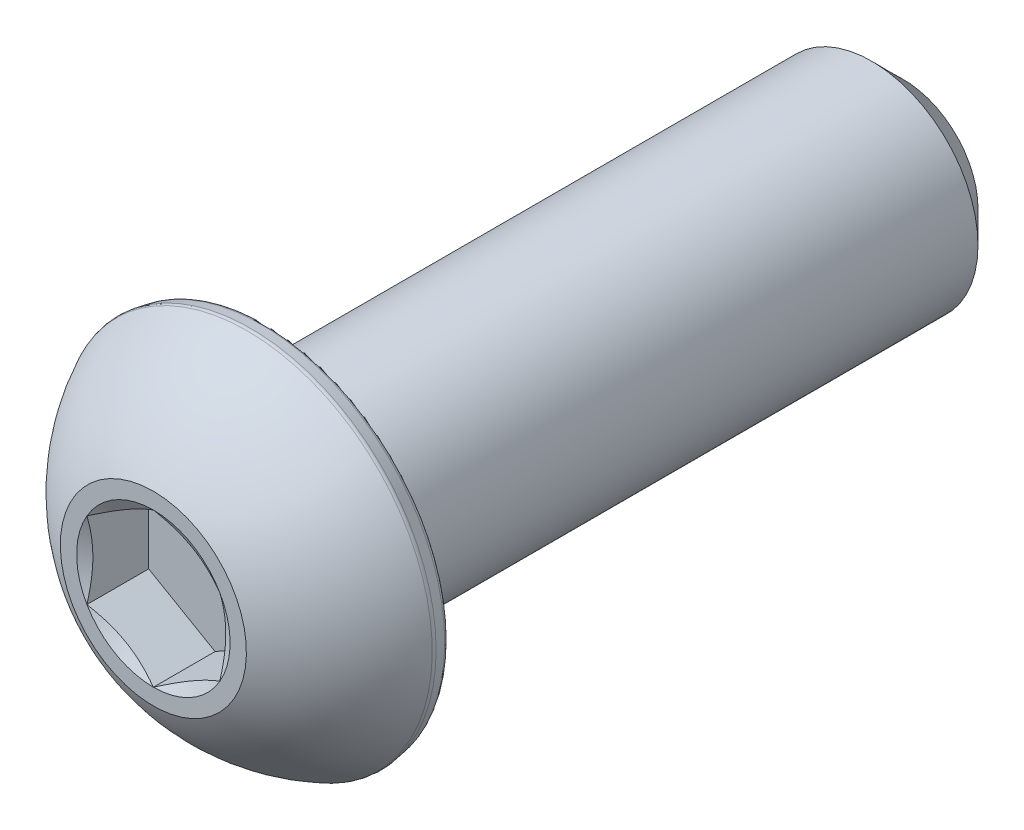
SolidWorks part; units mm, degrees
ref_plane "Front Plane" through (0, 0, 0) normal (0, 0, 1) x (1, 0, 0)
ref_plane "Top Plane" through (0, 0, 0) normal (0, 1, 0) x (1, 0, 0)
ref_plane "Right Plane" through (0, 0, 0) normal (1, 0, 0) x (0, 0, -1)
sketch "Sketch1" plane through (0, 0, 0) normal (1, 0, 0) x (0, 0, -1)
  line L0 (-11.2014, 0) -> (11.2014, 0) construction
  line L1 (-11.2014, 0) -> (-11.2014, 5.5499)
  line L2 (-11.2014, 5.5499) -> (-7.8486, 5.5499)
  line L3 (-7.8486, 5.5499) -> (-7.8486, 3.175)
  line L4 (-7.8486, 3.175) -> (11.2014, 3.175)
  line L5 (11.2014, 3.175) -> (11.2014, 0)
  point P2 (0, 0)
  point P4 (9.9314, 0)
  point P9 (9.2964, 3.175)
  point P10 (9.2964, -3.175)
  point P11 (11.2014, -3.175)
  point P15 (-9.3574, 0)
  dimension "Head Height" = 3.3528
  dimension "Head Diameter" = 11.0998
  dimension "Length" = 19.05
  dimension "Screw Size Decimal Equivalent" = 6.35
  dimension "Thread Pitch" = 1.27
  dimension "D1" = 1.905
  dimension "D2" = 1.844
sketch "Sketch2" plane through (0, 0, 0) normal (0, 0, 1) x (1, 0, 0)
  line L0 (0, 3.175) -> (0, 0) construction
  line L1 (0, 2.2914) -> (-1.9844, 1.1457)
  line L2 (-1.9844, 1.1457) -> (-1.9844, -1.1457)
  line L3 (-1.9844, -1.1457) -> (0, -2.2914)
  line L4 (0, -2.2914) -> (1.9844, -1.1457)
  line L5 (1.9844, -1.1457) -> (1.9844, 1.1457)
  line L6 (1.9844, 1.1457) -> (0, 2.2914)
  circle A0 centre (0, 0) radius 1.9844 construction
  circle A1 centre (0, 0) radius 2.7781
  point P10 (0, 2.7781)
  dimension "D1" = 5.5563
  dimension "Drive Size" = 3.9688
sketch "Sketch3" plane through (0, 0, 0) normal (1, 0, 0) x (0, 0, -1)
  line L0 (-11.2014, 0) -> (-11.2014, 2.7781)
  line L1 (-11.2014, 0) -> (-11.2014, 5.5499) construction
  line L2 (-11.2014, 5.5499) -> (-7.8486, 5.5499) construction
  line L3 (-8.3515, 5.5499) -> (-7.8486, 5.4612)
  line L4 (-7.8486, 5.5499) -> (-7.8486, 3.175) construction
  line L5 (-7.8486, 5.4612) -> (-7.8486, 3.175)
  line L6 (-11.2014, 0) -> (11.2014, 0) construction
  line L7 (-11.2014, 0) -> (11.2014, 0)
  line L8 (11.2014, 0) -> (11.2014, 2.2225)
  line L9 (11.2014, 3.175) -> (11.2014, 0) construction
  line L10 (11.2014, 2.2225) -> (10.2489, 3.175)
  line L11 (-7.8486, 3.175) -> (11.2014, 3.175) construction
  line L12 (10.2489, 3.175) -> (-7.8486, 3.175)
  arc A0 (-11.2014, 2.7781) -> (-8.3515, 5.5499) centre (-5.7266, 0) cw
  dimension "D1" = 0.5029
  dimension "D2" = 10
  dimension "D3" = 45
  dimension "D4" = 0.9525
revolve "Revolve1" add sketch "Sketch3" angle 360 about L7
sketch "Sketch4" plane through (0, 0, 11.2014) normal (0, 0, 1) x (1, 0, 0)
  line L0 (-1.9844, -1.1457) -> (0, -2.2914) construction
  line L1 (-1.9844, 1.1457) -> (-1.9844, -1.1457) construction
  line L2 (0, 2.2914) -> (-1.9844, 1.1457) construction
  line L3 (1.9844, 1.1457) -> (0, 2.2914) construction
  line L4 (1.9844, -1.1457) -> (1.9844, 1.1457) construction
  line L5 (0, -2.2914) -> (1.9844, -1.1457) construction
  line L6 (-1.9844, -1.1457) -> (0, -2.2914)
  line L7 (-1.9844, 1.1457) -> (-1.9844, -1.1457)
  line L8 (0, 2.2914) -> (-1.9844, 1.1457)
  line L9 (1.9844, 1.1457) -> (0, 2.2914)
  line L10 (1.9844, -1.1457) -> (1.9844, 1.1457)
  line L11 (0, -2.2914) -> (1.9844, -1.1457)
extrude "Cut-Extrude1" cut sketch "Sketch4" against normal up to vertex (1.844 mm away) up to point (0, 0, 9.3574)
sketch "Sketch5" plane through (0, 0, 11.2014) normal (0, 0, 1) x (1, 0, 0)
  circle A0 centre (0, 0) radius 2.2914
extrude "Cut-Extrude2" cut sketch "Sketch5" against normal up to vertex (1.844 mm away) draft 60 up to point (0, 0, 9.3574)
fillet "Fillet1" radius 0.1676 2 edges at (5.5499, 0, 8.3515) (5.4612, 0, 7.8486)
split "Split1" [suppressed] bodies to split 106
sketch "Sketch6" [suppressed] plane through (0, 0, -11.2014) normal (0, 0, -1) x (-1, 0, 0)
  circle A0 centre (0, 0) radius 3.175 construction
  circle A1 centre (0, 0) radius 3.175
curve "Helix/Spiral1" [suppressed] pitch 1.27 height 20.32 turns 16
sketch "Sketch7" [suppressed] plane through (0, 0, 0) normal (1, 0, 0) x (0, 0, -1)
  line L0 (11.122, 3.3125) -> (11.757, 2.2126) construction
  line L1 (11.757, 2.2126) -> (12.392, 3.3125) construction
  line L2 (12.392, 3.3125) -> (11.122, 3.3125) construction
  line L3 (11.1617, 3.2437) -> (12.3523, 3.2437)
  line L4 (12.3523, 3.2437) -> (11.8364, 2.3501)
  line L5 (11.8364, 2.3501) -> (11.6777, 2.3501)
  line L6 (11.6777, 2.3501) -> (11.1617, 3.2437)
  line L7 (11.757, 2.3501) -> (11.757, 2.2126) construction
  line L8 (11.2014, 3.175) -> (12.3127, 3.175) construction
  line L9 (11.757, 3.3125) -> (11.757, 3.175) construction
  point P12 (11.757, 3.2437)
  dimension "D1" = 1.27
  dimension "D2" = 0.1588
sweep "Cut-Sweep1" [suppressed] cut profiles "Sketch7" path "Helix/Spiral1"
sketch "Sketch8" [suppressed] plane through (0, 0, 7.8486) normal (0, 0, -1) x (-1, 0, 0)
  circle A0 centre (0, 0) radius 3.3125
extrude "Boss-Extrude1" [suppressed] add sketch "Sketch8" along normal up to vertex draft 45
equation "\"D1@Sketch1\"=\"Thread Pitch@Sketch1\"*1.5"
equation "\"D2@Sketch1\"=0.55*\"Head Height@Sketch1\""
equation "\"D1@Sketch2\"=\"Drive Size@Sketch2\"*1.4"
equation "\"D1@Sketch3\"=0.15*\"Head Height@Sketch1\""
equation "\"D4@Sketch3\"=0.75*\"Thread Pitch@Sketch1\""
equation "\"D1@Fillet1\"=.05*\"Head Height@Sketch1\""
equation "\"D4@Helix/Spiral1\"=\"Thread Pitch@Sketch1\""
equation "\"D3@Helix/Spiral1\"=\"Length@Sketch1\"+\"Thread Pitch@Sketch1\""
equation "\"D2@Sketch7\"=\"D1@Sketch7\"/8"
equation "\"D1@Sketch7\"=\"Thread Pitch@Sketch1\""
